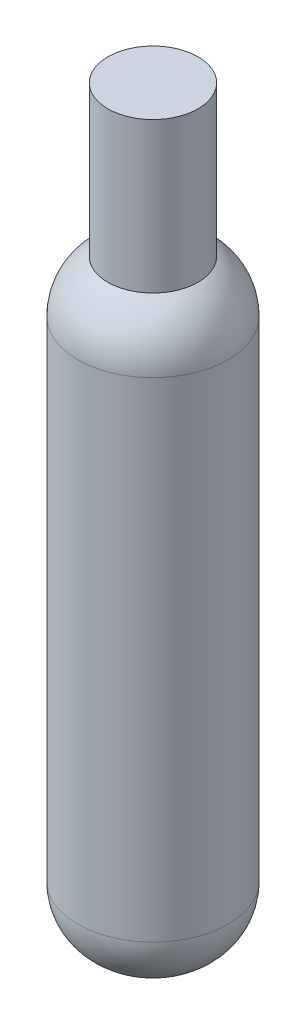
SolidWorks part; units mm, degrees
ref_plane "Alzado" through (0, 0, 0) normal (0, 0, 1) x (1, 0, 0)
ref_plane "Planta" through (0, 0, 0) normal (0, 1, 0) x (1, 0, 0)
ref_plane "Vista lateral" through (0, 0, 0) normal (1, 0, 0) x (0, 0, -1)
sketch "Croquis1" plane through (0, 0, 0) normal (0, 1, 0) x (1, 0, 0)
  circle A0 centre (0, 0) radius 2.5
extrude "Saliente-Extruir1" add sketch "Croquis1" along normal blind 20
fillet "Redondeo1" radius 2 1 edges at (0, 0, 2.5)
sketch "Croquis2" plane through (0, 0, 0) normal (0, -1, 0) x (1, 0, 0)
  circle A0 centre (0, 0) radius 1.5
extrude "Cortar-Extruir1" cut sketch "Croquis2" against normal blind 6
sketch "Croquis3" plane through (0, 20, 0) normal (0, 1, 0) x (1, 0, 0)
  circle A0 centre (0, 0) radius 1.5
extrude "Saliente-Extruir2" add sketch "Croquis3" along normal blind 5
fillet "Redondeo2" radius 2 1 edges at (0, 20, 2.5)
